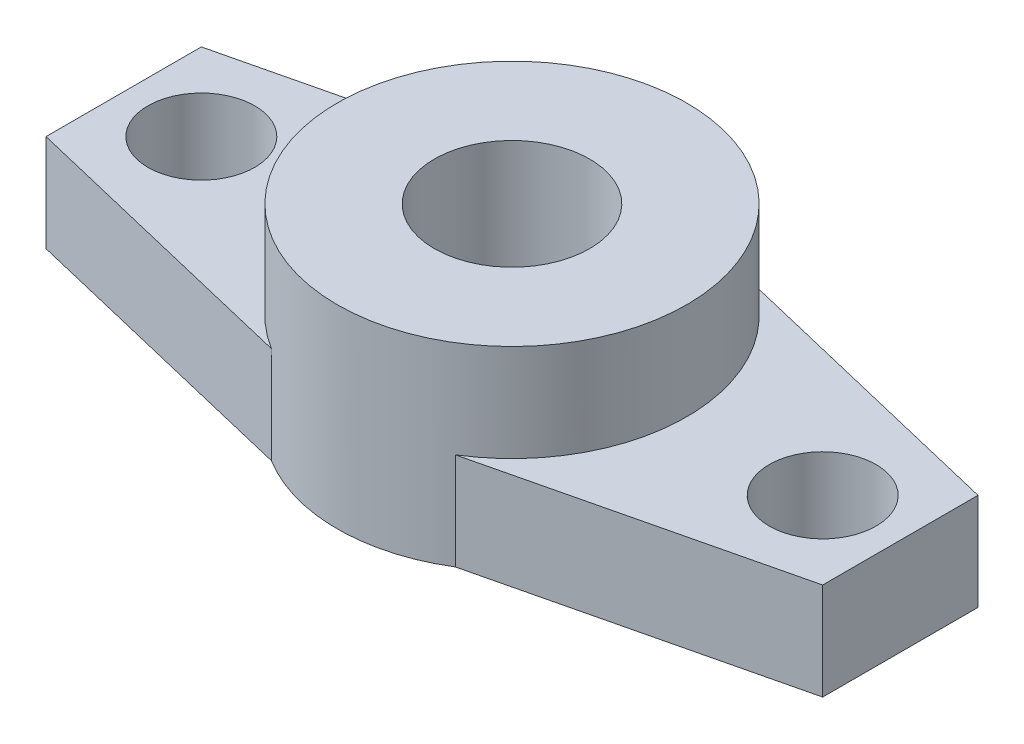
SolidWorks part; units mm, degrees
ref_plane "Plan de face" through (0, 0, 0) normal (0, 0, 1) x (1, 0, 0)
ref_plane "Plan de dessus" through (0, 0, 0) normal (0, 1, 0) x (1, 0, 0)
ref_plane "Plan de droite" through (0, 0, 0) normal (1, 0, 0) x (0, 0, -1)
sketch "Sketch1" plane through (0, 0, 0) normal (0, 1, 0) x (1, 0, 0)
  line L0 (-16, 0) -> (16, 0) construction
  line L1 (-20, 0) -> (20, 0) construction
  line L2 (-20, 4) -> (-20, -4)
  line L3 (-20, -4) -> (-4.7337, -7.6545)
  line L4 (-20, 4) -> (-4.7337, 7.6545)
  line L5 (0, 0) -> (0, -7.2537) construction
  line L6 (20, 4) -> (20, -4)
  line L7 (20, 4) -> (4.7337, 7.6545)
  line L8 (20, -4) -> (4.7337, -7.6545)
  circle A0 centre (0, 0) radius 4
  circle A1 centre (-16, 0) radius 2.75
  circle A2 centre (16, 0) radius 2.75
  circle A3 centre (0, 0) radius 9
  point P7 (0, 0)
  point P9 (0, 0)
  point P14 (-20, 0)
  point P22 (0, 0)
  dimension "D1" = 8
  dimension "D3" = 5.5
  dimension "D4" = 5.5
  dimension "D6" = 18
  dimension "D2" = 32
  dimension "D5" = 40
  dimension "D7" = 8
extrude "Boss-Extrude1" add sketch "Sketch1" along normal blind 5 contours A3 A0 | A3 L4 L2 L3 A1 | A3 L8 L6 L7 A2 region at (-12.7678, 0, 0) region at (0, 0, -8.7454) region at (12.7678, 0, 0)
extrude "Boss-Extrude2" add sketch "Sketch1<3>" along normal blind 10 contours A3 A0 region at (0, 0, -8.7454)
sketch "Sketch1<3>" plane through (0, 0, 0) normal (0, 1, 0) x (1, 0, 0) same geometry as "Sketch1"
